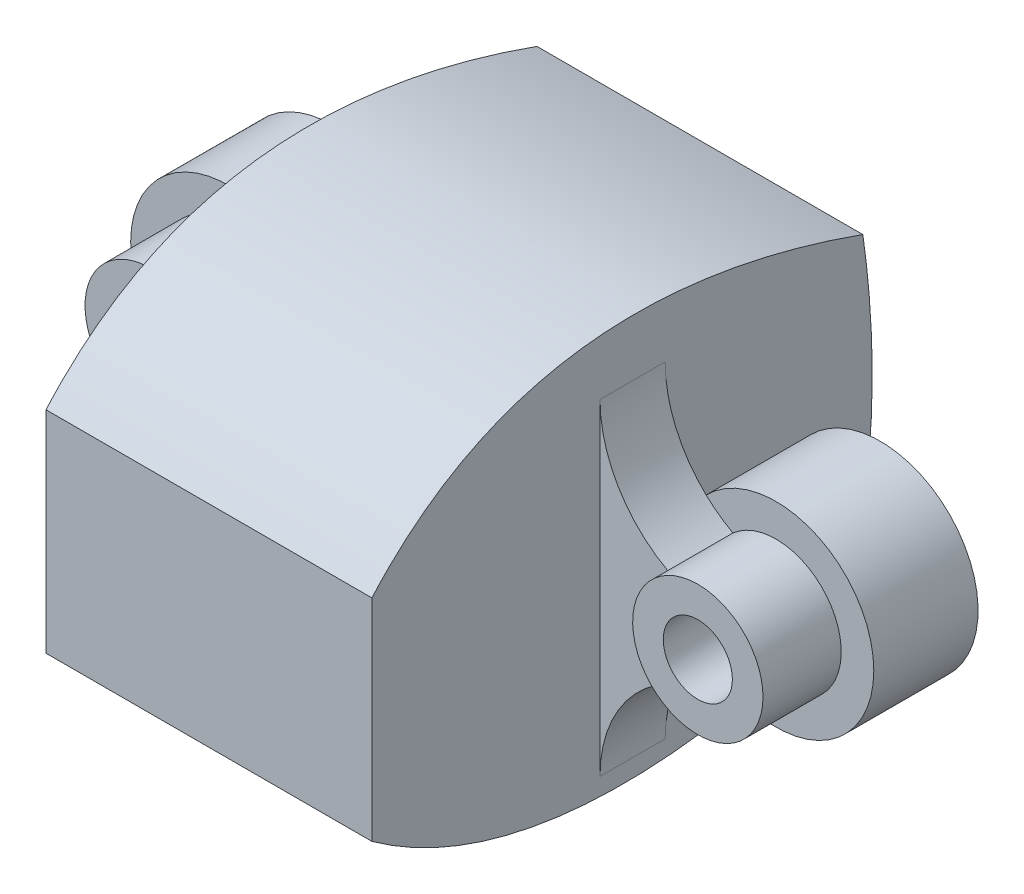
SolidWorks part; units mm, degrees
ref_plane "Front Plane" through (0, 0, 0) normal (0, 0, 1) x (1, 0, 0)
ref_plane "Top Plane" through (0, 0, 0) normal (0, 1, 0) x (1, 0, 0)
ref_plane "Right Plane" through (0, 0, 0) normal (1, 0, 0) x (0, 0, -1)
sketch "Sketch1" plane through (0, 0, 0) normal (1, 0, 0) x (0, 0, -1)
  line L0 (-19.0962, 121.2258) -> (-19.0962, 137.4045)
  spline S0 degree 2 poles (-19.0962, 137.4045) (-6.4675, 151.6991) (18.5686, 142.7118) knots 0 0 0 1 1 1
  spline S1 degree 2 poles (18.5686, 142.7118) (20.5155, 129.0566) (17.199, 118.5721) knots 0 0 0 1 1 1
  spline S2 degree 3 poles (17.199, 118.5721) (7.3552, 114.9342) (-7.5425, 112.8814) (-19.0962, 121.2258) knots 0 0 0 0 1 1 1 1
extrude "Boss-Extrude1" add sketch "Sketch1" along normal mid plane 25
sketch "Sketch3" plane through (0, 0, 0) normal (1, 0, 0) x (0, 0, -1)
  line L0 (0.9038, 129.3152) -> (-19.0962, 129.3152) construction
  line L1 (3.4038, 125.5652) -> (-1.5962, 125.5652)
  line L2 (3.4038, 125.5652) -> (3.4038, 133.0652)
  line L3 (3.4038, 133.0652) -> (-1.5962, 133.0652)
  line L4 (-1.5962, 125.5652) -> (-1.5962, 133.0652)
  line L5 (3.4038, 125.5652) -> (-1.5962, 133.0652) construction
  line L6 (3.4038, 133.0652) -> (-1.5962, 125.5652) construction
  line L7 (-19.0962, 137.4045) -> (-19.0962, 121.2258) construction
  point P4 (0.9038, 129.3152)
  dimension "D1" = 7.5
  dimension "D2" = 5
  dimension "D3" = 20
extrude "Boss-Extrude2" add sketch "Sketch3" along normal mid plane 55
sketch "Sketch4" plane through (0, 0, -3.4038) normal (0, 0, -1) x (-1, 0, 0)
  line L0 (-27.5, 129.3152) -> (27.5, 129.3152) construction
  line L1 (-27.5, 125.5652) -> (-27.5, 133.0652) construction
  line L2 (27.5, 125.5652) -> (27.5, 133.0652) construction
  circle A0 centre (-21.0048, 129.3152) radius 7.5
  circle A1 centre (21.0048, 129.3152) radius 7.5
  dimension "D1" = 15
extrude "Boss-Extrude3" add sketch "Sketch4" along normal blind 8
sketch "Sketch5" plane through (0, 0, -3.4038) normal (0, 0, 1) x (1, 0, 0)
  line L0 (0, 146.1811) -> (0, 115.4028) construction
  line L1 (12.5, 146.1811) -> (-12.5, 146.1811) construction
  line L2 (-12.5, 115.4028) -> (12.5, 115.4028) construction
  line L3 (-21.0048, 136.8152) -> (-31.11, 136.8152)
  line L4 (21.0048, 136.8152) -> (31.11, 136.8152)
  line L5 (21.0048, 136.8152) -> (21.0048, 119.4086)
  line L6 (21.0048, 119.4086) -> (31.11, 119.4086)
  line L7 (31.11, 136.8152) -> (31.11, 119.4086)
  line L8 (21.0048, 136.8152) -> (31.11, 119.4086) construction
  line L9 (21.0048, 119.4086) -> (31.11, 136.8152) construction
  line L10 (-21.0048, 136.8152) -> (-21.0048, 119.4086)
  line L11 (-21.0048, 119.4086) -> (-31.11, 119.4086)
  line L12 (-31.11, 136.8152) -> (-31.11, 119.4086)
  arc A0 (27.5, 133.0652) -> (14.5096, 133.0652) centre (21.0048, 129.3152) ccw construction
  point P10 (26.0574, 128.1119)
extrude "Cut-Extrude1" cut sketch "Sketch5" along normal through all
sketch "Sketch6" plane through (0, 0, -3.4038) normal (0, 0, 1) x (1, 0, 0)
  line L0 (21.0048, 133.0652) -> (21.0048, 125.5652) construction
  line L1 (-21.0048, 125.5652) -> (-21.0048, 133.0652) construction
  circle A0 centre (21.0048, 129.3152) radius 5
  circle A1 centre (-21.0048, 129.3152) radius 5
  dimension "D1" = 10
extrude "Boss-Extrude4" add sketch "Sketch6" along normal blind 6
fillet "Fillet1" radius 10 4 edges at (12.5, 125.5652, -0.9038) (12.5, 133.0652, -0.9038) (-12.5, 133.0652, -0.9038) (-12.5, 125.5652, -0.9038)
sketch "Sketch7" plane through (0, 0, 2.5962) normal (0, 0, 1) x (1, 0, 0)
  circle A0 centre (21.0048, 129.3152) radius 2.65
  circle A1 centre (-21.0048, 129.3152) radius 2.65
  dimension "D1" = 5.3
extrude "Cut-Extrude2" cut sketch "Sketch7" against normal blind 6
ref_plane "Plane1" through (0, 0, -0.9038) normal (0, 0, 1) x (1, 0, 0)
sketch "Sketch8" plane through (0, 0, -0.9038) normal (0, 0, 1) x (1, 0, 0)
  line L0 (21.0048, 129.3152) -> (-21.0048, 129.3152) construction
  point P4 (0, 129.3152)
move or copy body "Body-Move/Copy1" bodies to move or copy 106 copy no translate (0, -129.32, -0.9)
sketch "Sketch10" plane through (0, 0, -4.3038) normal (0, 0, -1) x (-1, 0, 0)
  line L1 (-12.5, 16.8611) -> (12.5, 16.8611)
  line L2 (-12.5, 16.8611) -> (-12.5, -13.9172)
  line L3 (-12.5, -13.9172) -> (12.5, -13.9172)
  line L4 (12.5, 16.8611) -> (12.5, -13.9172)
  line L5 (-12.5, 16.8611) -> (12.5, -13.9172) construction
  line L6 (-12.5, -13.9172) -> (12.5, 16.8611) construction
  point P4 (0, 1.4719)
extrude "Cut-Extrude3" [suppressed] cut sketch "Sketch10" along normal through all
sketch "Sketch11" plane through (0, 0, 0.6962) normal (0, 0, 1) x (1, 0, 0)
  line L0 (12.5, -13.9172) -> (12.5, -8.0942) construction
  line L1 (-12.5, 16.8611) -> (12.5, 16.8611)
  line L2 (-12.5, 16.8611) -> (-12.5, -16.4911)
  line L3 (-12.5, -16.4911) -> (12.5, -16.4911)
  line L4 (12.5, 16.8611) -> (12.5, -16.4911)
  line L5 (-12.5, 16.8611) -> (12.5, -16.4911) construction
  line L6 (-12.5, -16.4911) -> (12.5, 16.8611) construction
  point P4 (0, 0.185)
extrude "Cut-Extrude4" [suppressed] cut sketch "Sketch11" along normal through all
sketch "Sketch12" plane through (0, 0, 0.6962) normal (0, 0, 1) x (1, 0, 0)
  line L1 (-17.6976, 3.7452) -> (17.6976, 3.7452)
  line L2 (-17.6976, 3.7452) -> (-17.6976, 19.0947)
  line L3 (-17.6976, 19.0947) -> (17.6976, 19.0947)
  line L4 (17.6976, 3.7452) -> (17.6976, 19.0947)
  line L5 (-17.6976, 3.7452) -> (17.6976, 19.0947) construction
  line L6 (-17.6976, 19.0947) -> (17.6976, 3.7452) construction
  line L7 (-17.6976, -3.7548) -> (17.6976, -3.7548)
  line L8 (-17.6976, -3.7548) -> (-17.6976, -18.2927)
  line L9 (-17.6976, -18.2927) -> (17.6976, -18.2927)
  line L10 (17.6976, -3.7548) -> (17.6976, -18.2927)
  line L11 (-17.6976, -3.7548) -> (17.6976, -18.2927) construction
  line L12 (-17.6976, -18.2927) -> (17.6976, -3.7548) construction
  point P4 (0, 11.4199)
  point P12 (0, -11.0238)
extrude "Cut-Extrude5" [suppressed] cut sketch "Sketch12" against normal up to surface (5 mm away) up to face at (21.9385, -0.0048, -4.3038)
sketch "Sketch13" [suppressed] plane through (0, 0, -4.3038) normal (0, 0, 1) x (1, 0, 0)
  line L0 (17.6976, -3.7548) -> (-17.6976, -3.7548) construction
  line L1 (-17.6976, 3.7452) -> (17.6976, 3.7452) construction
  line L2 (14.5096, 3.7452) -> (17.6976, 3.7452)
  line L3 (17.6976, -3.7548) -> (14.5096, -3.7548)
  line L6 (-17.6976, 3.7452) -> (-14.5096, 3.7452)
  line L7 (-14.5096, -3.7548) -> (-17.6976, -3.7548)
  line L10 (14.5096, -3.7548) -> (-14.5096, -3.7548)
  line L11 (-14.5096, 3.7452) -> (14.5096, 3.7452)
  circle A0 centre (21.0048, -0.0048) radius 2.65 construction
  circle A1 centre (-21.0048, -0.0048) radius 2.65 construction
  arc A2 (14.5096, -3.7548) -> (14.5096, 3.7452) centre (21.0048, -0.0048) ccw
  arc A3 (17.6976, -3.7548) -> (17.6976, 3.7452) centre (21.0048, -0.0048) ccw
  arc A4 (14.5096, -3.7548) -> (14.5096, 3.7452) centre (21.0048, -0.0048) ccw
  arc A6 (-17.6976, 3.7452) -> (-17.6976, -3.7548) centre (-21.0048, -0.0048) ccw
  arc A7 (-14.5096, 3.7452) -> (-14.5096, -3.7548) centre (-21.0048, -0.0048) ccw
  arc A9 (-14.5096, 3.7452) -> (-14.5096, -3.7548) centre (-21.0048, -0.0048) ccw
  circle A10 centre (21.0048, -0.0048) radius 2.65
  circle A11 centre (-21.0048, -0.0048) radius 2.65
  dimension "D1" = 0
  dimension "D2" = 0
extrude "Boss-Extrude5" [suppressed] add sketch "Sketch13" along normal up to surface (6 mm away) up to face at (-18.3548, -0.0048, 1.6962)
sketch "Sketch14" plane through (0, 0, -4.3038) normal (0, 0, -1) x (-1, 0, 0)
  line L1 (12.5, 12.5165) -> (12.5, -12.5262)
  line L2 (12.5, 12.5165) -> (12.5, -12.5262)
  arc A2 (15.6422, 5.2385) -> (15.6422, -5.2482) centre (21.0048, -0.0048) ccw
  arc A3 (12.5, 12.5165) -> (15.6422, 5.2385) centre (22.5, 12.5165) ccw
  arc A4 (15.6422, 5.2385) -> (15.6422, -5.2482) centre (21.0048, -0.0048) ccw
  arc A7 (12.5, 12.5165) -> (15.6422, 5.2385) centre (22.5, 12.5165) ccw
  arc A8 (15.6422, -5.2482) -> (12.5, -12.5262) centre (22.5, -12.5262) ccw
  arc A9 (15.6422, -5.2482) -> (12.5, -12.5262) centre (22.5, -12.5262) ccw
  dimension "D1" = 0
extrude "Boss-Extrude6" [suppressed] add sketch "Sketch14" along normal up to surface (8 mm away) up to face at (13.5048, -0.0048, -12.3038)
